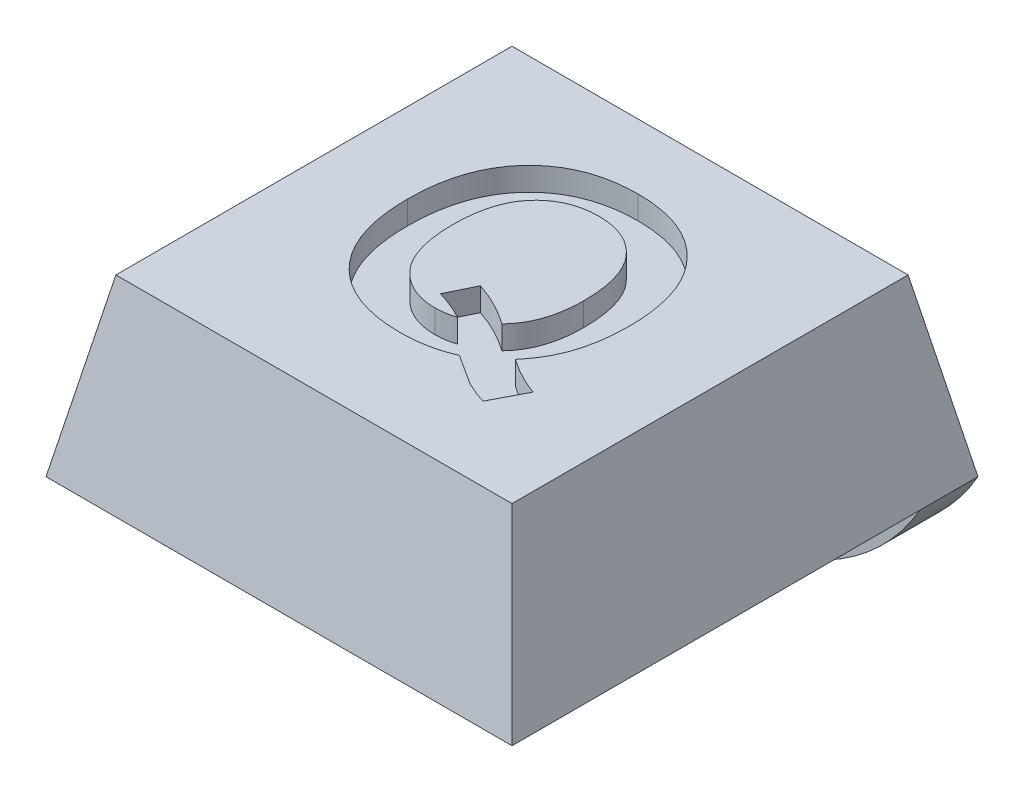
SolidWorks part; units mm, degrees
ref_plane "Front Plane" through (0, 0, 0) normal (0, 0, 1) x (1, 0, 0)
ref_plane "Top Plane" through (0, 0, 0) normal (0, 1, 0) x (1, 0, 0)
ref_plane "Right Plane" through (0, 0, 0) normal (1, 0, 0) x (0, 0, -1)
sketch "Sketch1" plane through (0, 0, 0) normal (0, 1, 0) x (1, 0, 0)
  line L1 (0, 0) -> (8, 0)
  line L2 (0, 0) -> (0, 8)
  line L3 (0, 8) -> (8, 8)
  line L4 (8, 0) -> (8, 8)
  dimension "D1" = 8
  dimension "D2" = 8
extrude "Boss-Extrude1" add sketch "Sketch1" along normal blind 3
sketch "Sketch2" plane through (0, 0, 0) normal (0, 0, 1) x (1, 0, 0)
  line L0 (0, 0) -> (0.6, 3)
  line L1 (0, 3) -> (8, 3) construction
  line L2 (0.6, 3) -> (0, 3)
  line L3 (0, 3) -> (0, 0)
  line L4 (8, 0) -> (7.4, 3)
  line L5 (7.4, 3) -> (8, 3)
  line L6 (8, 3) -> (8, 0)
  dimension "D1" = 0.6
  dimension "D2" = 0.6
extrude "Cut-Extrude1" cut sketch "Sketch2" against normal through all both and the other way through all
sketch "Sketch3" plane through (0, 0, 0) normal (1, 0, 0) x (0, 0, -1)
  line L0 (0, 0) -> (0.6, 3)
  line L1 (8, 3) -> (0, 3) construction
  line L2 (0.6, 3) -> (0, 3)
  line L3 (0, 3) -> (0, 0)
  line L4 (8, 3) -> (7.4, 3)
  line L5 (7.4, 3) -> (8, 0)
  line L6 (8, 3) -> (8, 0)
  dimension "D1" = 0.6
  dimension "D2" = 0.6
extrude "Cut-Extrude2" cut sketch "Sketch3" along normal blind 11
sketch "Sketch4" plane through (0, 0, 0) normal (0, -1, 0) x (1, 0, 0)
  line L0 (8, 0) -> (8, -8) construction
  line L3 (0, 0) -> (8, 0) construction
  circle A0 centre (4, -3.75) radius 1.8
  dimension "D1" = 3.6
  dimension "D2" = 4
  dimension "D3" = 3.75
extrude "Cut-Extrude3" cut sketch "Sketch4" against normal blind 0.8
sketch "Sketch5" plane through (0, 0, 0) normal (0, -1, 0) x (1, 0, 0)
  line L0 (8, 0) -> (8, -8) construction
  line L1 (0, -8) -> (8, -8)
  line L2 (0, -8) -> (0, -7)
  line L3 (0, -7) -> (8, -7)
  line L4 (8, -8) -> (8, -7)
  dimension "D1" = 1
extrude "Boss-Extrude2" add sketch "Sketch5" along normal blind 2
fillet "Fillet1" radius 4 2 edges at (8, -2, -7.5) (0, -2, -7.5)
sketch "Sketch6" plane through (0, 3, 0) normal (0, 1, 0) x (1, 0, 0)
  text T0 "Q" font "Arial" height 4
extrude "Cut-Extrude4" cut sketch "Sketch6" against normal blind 0.4
